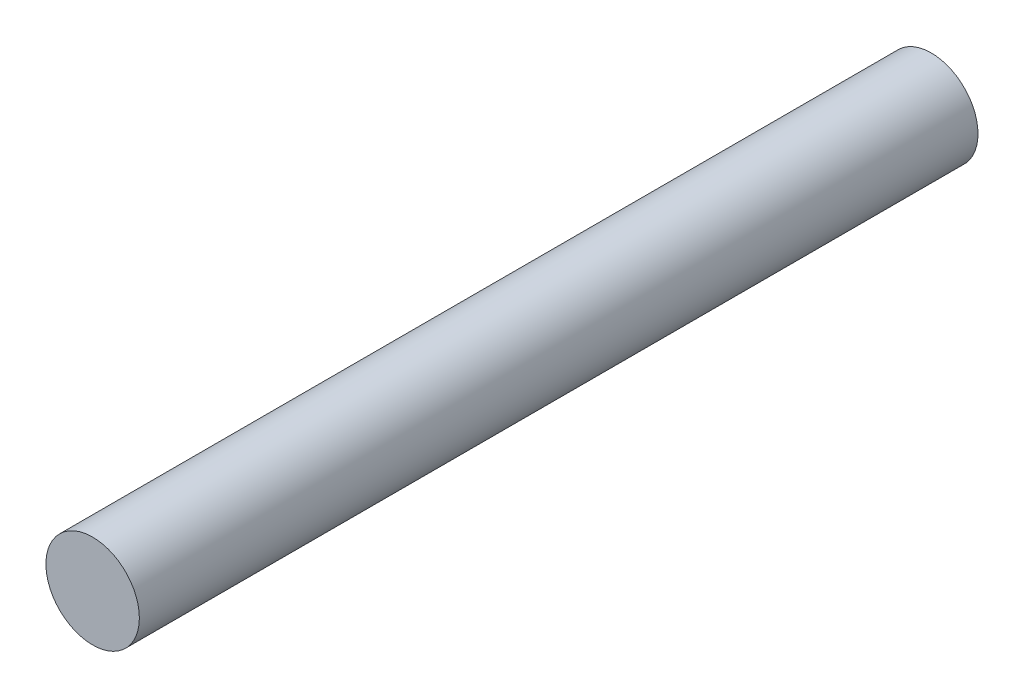
SolidWorks part; units mm, degrees
ref_plane "Front Plane" through (0, 0, 0) normal (0, 0, 1) x (1, 0, 0)
ref_plane "Top Plane" through (0, 0, 0) normal (0, 1, 0) x (1, 0, 0)
ref_plane "Right Plane" through (0, 0, 0) normal (1, 0, 0) x (0, 0, -1)
sketch "Sketch1" plane through (0, 0, 0) normal (0, 0, 1) x (1, 0, 0)
  circle A0 centre (0, 0) radius 3.9
  dimension "D1" = 7.8
extrude "Boss-Extrude1" add sketch "Sketch1" along normal blind 70
